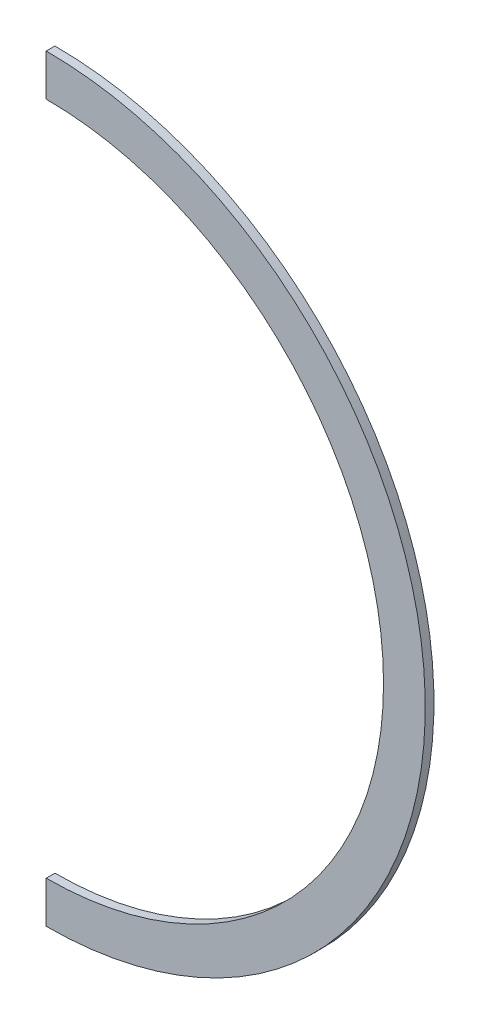
SolidWorks part; units mm, degrees
material "Balsa"
ref_plane "Front Plane" through (0, 0, 0) normal (0, 0, 1) x (1, 0, 0)
ref_plane "Top Plane" through (0, 0, 0) normal (0, 1, 0) x (1, 0, 0)
ref_plane "Right Plane" through (0, 0, 0) normal (1, 0, 0) x (0, 0, -1)
sketch "Sketch1" plane through (0, 0, 0) normal (0, 0, 1) x (1, 0, 0)
  line L0 (0, 32.094) -> (0, -346.2619) construction
  line L1 (0, 0) -> (0, 244.345) construction
  line L2 (0, 0) -> (0, 471.6969) construction
  line L3 (0, 0) -> (-283.5939, 0) construction
  line L4 (-127.2933, -32.5553) -> (-85.9841, -73.8644)
  line L5 (-85.9841, -73.8644) -> (-85.9841, -86.6438)
  line L6 (-85.9841, -73.8644) -> (-54.3993, -105.4493) construction
  arc A0 (-54.3993, -105.4493) -> (-127.2933, -32.5553) centre (0, 21.844) ccw
  arc A2 (-82.075, -89.6305) -> (-54.3993, -105.4493) centre (0, 21.844) ccw construction
  arc A3 (-127.2933, -32.5553) -> (-82.075, -89.6305) centre (0, 21.844) ccw construction
  arc A4 (-85.9841, -86.6438) -> (-54.3993, -105.4493) centre (0, 21.844) ccw
  spline S2 degree 3 poles (-1530.9406, -7642.7149) (259.0907, -1408.3953) (378.6573, 10.519) (49.9381, 150.9258) (45.7097, 152.4909) (37.1079, 155.2035) (32.7346, 156.3511) (27.1752, 157.5183) (26.0587, 157.7384) (23.8163, 158.1514) (22.6888, 158.3447) (19.306, 158.8811) (17.0511, 159.1813) (10.2867, 159.9126) (1.2693, 160.4377) (-7.745, 160.0789) (-14.5046, 159.4749) (-16.7575, 159.2176) (-20.1367, 158.7464) (-21.263, 158.5751) (-23.5156, 158.2037) (-24.6421, 158.0036) (-30.2426, 156.9366) (-34.6466, 155.8674) (-43.3063, 153.3113) (-47.562, 151.8242) (-55.9254, 148.4331) (-60.0331, 146.529) (-66.0807, 143.3516) (-68.0818, 142.2359) (-72.0044, 139.9197) (-73.9301, 138.7173) (-79.6017, 134.9792) (-86.884, 129.6473) (-93.6143, 123.6295) (-98.4521, 118.8554) (-100.0296, 117.2204) (-102.3424, 114.7015) (-103.1054, 113.8496) (-104.6077, 112.1297) (-105.3467, 111.2623) (-108.9818, 106.8875) (-111.6981, 103.2683) (-116.7574, 95.7975) (-119.1004, 91.9459) (-123.4121, 84.0098) (-125.3809, 79.9253) (-127.6006, 74.6695) (-128.0327, 73.61) (-128.8681, 71.4874) (-129.2719, 70.423) (-130.4422, 67.2205) (-131.1674, 65.0732) (-133.1812, 58.5951) (-135.4347, 49.861) (-136.834, 40.9354) (-137.5569, 34.168) (-137.7434, 31.9) (-137.9397, 28.4793) (-137.9911, 27.3374) (-138.0656, 25.0596) (-138.0887, 23.9223) (-138.135, 18.2442) (-137.9496, 13.7276) (-137.1441, 4.7454) (-136.5239, 0.2797) (-134.8456, -8.6005) (-133.7876, -13.015) (-131.2181, -21.791) (-129.7278, -26.0794) (-126.351, -34.4622) (-124.4643, -38.5569) (-120.2966, -46.5538) (-118.0156, -50.456) (-114.9122, -55.2108) (-114.2789, -56.1556) (-112.9868, -58.0327) (-112.3272, -58.9661) (-110.315, -61.7398) (-108.9333, -63.5482) (-104.6702, -68.8537) (-98.6716, -75.6089) (-92.0553, -81.7381) (-86.8592, -86.0978) (-85.0881, -87.5114) (-82.3719, -89.5716) (-81.4566, -90.2482) (-79.6058, -91.5811) (-78.6696, -92.238) (312.7351, -359.6403) (1980.7618, 1435.5712) (5240.7041, 5800.1077) knots -2.409432 -2.409432 -2.409432 -2.409432 0.03125 0.03125 0.0625 0.0625 0.09375 0.09375 0.101563 0.101563 0.109375 0.109375 0.125 0.125 0.15625 0.1875 0.1875 0.203125 0.203125 0.210937 0.210937 0.21875 0.21875 0.25 0.25 0.28125 0.28125 0.3125 0.3125 0.328125 0.328125 0.34375 0.34375 0.375 0.40625 0.40625 0.421875 0.421875 0.429687 0.429687 0.4375 0.4375 0.46875 0.46875 0.5 0.5 0.53125 0.53125 0.539062 0.539062 0.546875 0.546875 0.5625 0.5625 0.59375 0.625 0.625 0.640625 0.640625 0.648437 0.648437 0.65625 0.65625 0.6875 0.6875 0.71875 0.71875 0.75 0.75 0.78125 0.78125 0.8125 0.8125 0.84375 0.84375 0.851562 0.851562 0.859375 0.859375 0.875 0.875 0.90625 0.9375 0.9375 0.953125 0.953125 0.960937 0.960937 0.96875 0.96875 4.2021 4.2021 4.2021 4.2021 only from (66.3397, 143.1887) to (-66.0465, -100.0388)
  spline S3 degree 3 poles (66.3397, 143.1887) (62.3323, 145.3909) (58.2494, 147.3758) (49.9381, 150.9258) (45.7097, 152.4909) (37.1079, 155.2035) (32.7346, 156.3511) (27.1752, 157.5183) (26.0587, 157.7384) (23.8163, 158.1514) (22.6888, 158.3447) (19.306, 158.8811) (17.0511, 159.1813) (10.2867, 159.9126) (1.2693, 160.4377) (-7.745, 160.0789) (-14.5046, 159.4749) (-16.7575, 159.2176) (-20.1367, 158.7464) (-21.263, 158.5751) (-23.5156, 158.2037) (-24.6421, 158.0036) (-30.2426, 156.9366) (-34.6466, 155.8674) (-43.3063, 153.3113) (-47.562, 151.8242) (-55.9254, 148.4331) (-60.0331, 146.529) (-66.0807, 143.3516) (-68.0818, 142.2359) (-72.0044, 139.9197) (-73.9301, 138.7173) (-79.6017, 134.9792) (-86.884, 129.6473) (-93.6143, 123.6295) (-98.4521, 118.8554) (-100.0296, 117.2204) (-102.3424, 114.7015) (-103.1054, 113.8496) (-104.6077, 112.1297) (-105.3467, 111.2623) (-108.9818, 106.8875) (-111.6981, 103.2683) (-116.7574, 95.7975) (-119.1004, 91.9459) (-123.4121, 84.0098) (-125.3809, 79.9253) (-127.6006, 74.6695) (-128.0327, 73.61) (-128.8681, 71.4874) (-129.2719, 70.423) (-130.4422, 67.2205) (-131.1674, 65.0732) (-133.1812, 58.5951) (-135.4347, 49.861) (-136.834, 40.9354) (-137.5569, 34.168) (-137.7434, 31.9) (-137.9397, 28.4793) (-137.9911, 27.3374) (-138.0656, 25.0596) (-138.0887, 23.9223) (-138.135, 18.2442) (-137.9496, 13.7276) (-137.1441, 4.7454) (-136.5239, 0.2797) (-134.8456, -8.6005) (-133.7876, -13.015) (-131.2181, -21.791) (-129.7278, -26.0794) (-127.6847, -31.1513) (-127.3213, -32.0275) (-126.9491, -32.8995) knots 0 0 0 0 0.03125 0.03125 0.0625 0.0625 0.09375 0.09375 0.101563 0.101563 0.109375 0.109375 0.125 0.125 0.15625 0.1875 0.1875 0.203125 0.203125 0.210937 0.210937 0.21875 0.21875 0.25 0.25 0.28125 0.28125 0.3125 0.3125 0.328125 0.328125 0.34375 0.34375 0.375 0.40625 0.40625 0.421875 0.421875 0.429687 0.429687 0.4375 0.4375 0.46875 0.46875 0.5 0.5 0.53125 0.53125 0.539062 0.539062 0.546875 0.546875 0.5625 0.5625 0.59375 0.625 0.625 0.640625 0.640625 0.648437 0.648437 0.65625 0.65625 0.6875 0.6875 0.71875 0.71875 0.75 0.75 0.78125 0.78125 0.787815 0.787815 0.787815 0.787815 construction
  point P2 (0, 160.2226)
  point P3 (0, -116.9127)
  point P23 (-85.9841, -73.8644)
  dimension "D1" = 277.1353
  dimension "D2" = 276.86
  dimension "D3" = 21.844
  dimension "D5" = 45
  dimension "D6" = 113.03
  dimension "D4" = 58.42
  dimension "D7" = 45
extrude "Boss-Extrude1" add sketch "Sketch1" along normal mid plane 3.175
sketch "Sketch2" plane through (0, 0, 1.5875) normal (0, 0, 1) x (1, 0, 0)
  line L4 (-114.3729, -23.9231) -> (-70.7441, -67.5518)
  line L5 (-70.7441, -67.5518) -> (-70.7441, -79.0076)
  line L6 (-114.3729, -23.9231) -> (-70.7441, -67.5518)
  line L7 (-70.7441, -67.5518) -> (-70.7441, -79.0076)
  arc A2 (-70.7441, -79.0076) -> (-114.3729, -23.9231) centre (0, 21.844) ccw
  arc A3 (-70.7441, -79.0076) -> (-114.3729, -23.9231) centre (0, 21.844) ccw
  dimension "D1" = 15.24
extrude "Cut-Extrude1" cut sketch "Sketch2" against normal up to surface (3.175 mm away) up to face at (-27.5361, -9.1994, -1.5875)
fillet "Fillet1" radius 8.89 6 edges at (-127.2933, -32.5553, 0) (-114.3729, -23.9231, 0) (-85.9841, -73.8644, 0) (-85.9841, -86.6438, 0) (-70.7441, -67.5518, 0) (-70.7441, -79.0076, 0)
sketch "Sketch3" plane through (0, 0, 1.5875) normal (0, 0, 1) x (1, 0, 0)
  line L0 (-0.0002, 49.9919) -> (-0.0176, 733.2) construction
  line L1 (-0.0002, 49.9919) -> (-0.0176, 733.2) construction
  line L2 (-136.2041, -28.3557) -> (-0.0002, 49.9919) construction
  line L3 (136.2076, -28.3488) -> (-0.0002, 49.9919) construction
  line L4 (-136.2041, -28.3557) -> (-0.0002, 49.9919) construction
  line L5 (136.2076, -28.3488) -> (-0.0002, 49.9919) construction
  line L6 (-1.6539, 152.6441) -> (-1.654, 160.2641)
  line L7 (1.6481, 152.6442) -> (1.648, 160.2642)
  line L8 (-1.6539, 152.6441) -> (1.6481, 152.6442)
  line L9 (119.8485, -45.962) -> (106.7537, -38.3747)
  line L10 (121.4435, -43.2066) -> (108.3479, -35.6188)
  line L11 (-126.0584, -33.7901) -> (-88.588, -71.2606)
  line L12 (-85.9841, -77.5468) -> (-85.9841, -82.2574)
  line L13 (-126.0584, -33.7901) -> (-88.588, -71.2606) construction
  line L14 (-85.9841, -77.5468) -> (-85.9841, -82.2574) construction
  line L18 (121.4435, -43.2066) -> (108.3479, -35.6188)
  line L30 (-123.167, -47.8929) -> (-104.8722, -37.2914)
  line L35 (119.8485, -45.962) -> (106.7537, -38.3747)
  line L47 (108.5244, -35.721) -> (120.1169, -46.1175) construction
  line L48 (114.3206, -40.9193) -> (126.5619, -48.0121) construction
  line L49 (113.8577, -42.5592) -> (122.0137, -47.2849)
  line L50 (115.5132, -39.7021) -> (123.6691, -44.4278)
  line L51 (113.8577, -42.5592) -> (115.5132, -39.7021)
  line L52 (122.0137, -47.2849) -> (123.6691, -44.4278)
  line L58 (-124.7703, -45.1423) -> (-106.4681, -34.5364)
  line L59 (-124.7703, -45.1423) -> (-123.167, -47.8929)
  line L71 (-124.7703, -45.1423) -> (-123.167, -47.8929) construction
  line L72 (-124.7703, -45.1423) -> (-106.4681, -34.5364) construction
  line L73 (-123.167, -47.8929) -> (-104.8722, -37.2914) construction
  line L74 (-123.167, -47.8929) -> (-107.9499, -35.3951) construction
  line L75 (-115.5584, -41.644) -> (-110.9064, -38.9482) construction
  line L76 (-119.3826, -41.9518) -> (-112.6266, -38.0369)
  line L77 (-117.727, -44.8088) -> (-110.971, -40.8938)
  line L78 (-119.3826, -41.9518) -> (-117.727, -44.8088)
  line L79 (-112.6266, -38.0369) -> (-110.971, -40.8938)
  arc A0 (-54.3993, -105.4493) -> (-127.2933, -32.5553) centre (0, 21.844) ccw construction
  arc A2 (-1.654, 160.2641) -> (-130.2816, -24.9489) centre (0, 21.844) ccw construction
  arc A3 (-130.2816, -24.9489) -> (-127.2933, -32.5553) centre (0, 21.844) ccw construction
  arc A4 (-1.654, 160.2641) -> (-130.2816, -24.9489) centre (0, 21.844) ccw construction
  arc A5 (-130.2816, -24.9489) -> (-127.9919, -30.8906) centre (0, 21.844) ccw construction
  arc A6 (-82.3849, -89.4016) -> (-127.9919, -30.8906) centre (0, 21.844) ccw
  arc A7 (-127.9919, -30.8906) -> (-126.0584, -33.7901) centre (-119.7722, -27.504) ccw
  arc A8 (-85.9841, -77.5468) -> (-88.588, -71.2606) centre (-94.8741, -77.5468) ccw
  arc A9 (-85.9841, -82.2574) -> (-82.3849, -89.4016) centre (-77.0941, -82.2574) ccw
  arc A11 (-127.9919, -30.8906) -> (-126.0584, -33.7901) centre (-119.7722, -27.504) ccw construction
  arc A12 (-85.9841, -77.5468) -> (-88.588, -71.2606) centre (-94.8741, -77.5468) ccw construction
  arc A13 (-85.9841, -82.2574) -> (-82.3849, -89.4016) centre (-77.0941, -82.2574) ccw construction
  arc A14 (130.2841, -24.9419) -> (1.648, 160.2642) centre (0, 21.844) ccw construction
  arc A15 (1.648, 160.2642) -> (-1.654, 160.2641) centre (0, 21.844) ccw
  arc A16 (130.2841, -24.9419) -> (1.648, 160.2642) centre (0, 21.844) ccw construction
  arc A17 (1.648, 160.2642) -> (-1.654, 160.2641) centre (0, 21.844) ccw
  spline S0 degree 3 poles (106.7537, -38.3747) (107.2851, -37.456) (107.8165, -36.5374) (108.3479, -35.6188) knots 0 0 0 0 1 1 1 1 weights 1 1 1 1
  spline S1 degree 3 poles (119.8485, -45.962) (120.3802, -45.0435) (120.9118, -44.1251) (121.4435, -43.2066) knots 0 0 0 0 1 1 1 1 weights 1 1 1 1
  spline S2 degree 3 poles (-885.9096, -1769.7959) (-211.5315, -623.0099) (457.4335, 532.6653) (1115.294, 1687.3986) knots -628.025755 -628.025755 -628.025755 -628.025755 629.32196 629.32196 629.32196 629.32196 weights 1.00213 0.999289 0.99929 1.002132 only from (119.8485, -45.962) to (121.4435, -43.2066)
  spline S3 degree 3 poles (-1102.963, 1696.4301) (-441.8978, 540.8873) (227.2768, -614.259) (901.012, -1762.8827) knots -628.210575 -628.210575 -628.210575 -628.210575 629.142222 629.142222 629.142222 629.142222 weights 1.001328 0.999558 0.999557 1.001327 only from (-106.4681, -34.5364) to (-104.8722, -37.2914)
  spline S4 degree 3 poles (-106.4681, -34.5364) (-105.9361, -35.4547) (-105.4042, -36.373) (-104.8722, -37.2914) knots 0 0 0 0 1 1 1 1 weights 1 1 1 1 construction
  spline S6 degree 3 poles (-898.3985, -1763.0369) (-224.3104, -615.0446) (444.2624, 540.7506) (1102.1878, 1695.4772) knots -627.922228 -627.922228 -627.922228 -627.922228 629.425892 629.425892 629.425892 629.425892 weights 1.001921 0.999359 0.99936 1.001924 only from (106.7537, -38.3747) to (108.3479, -35.6188)
  point P49 (-116.0256, -43.8229)
  point P50 (120.451, -46.3794)
  arc M19 (-82.3849, -89.4016) -> (-127.9919, -30.8906) centre (0, 21.844) ccw
  line M21 (-126.0584, -33.7901) -> (-88.588, -71.2606)
  dimension "D1" = 3.302
  dimension "D2" = 7.62
  dimension "D4" = 3.302
  dimension "D5" = 7.62
  dimension "D6" = 3.302
  dimension "D7" = 5.842
  dimension "D3" = 0
extrude "Cut-Extrude2" [suppressed] cut sketch "Sketch3" against normal through all contours L79 L76 L77 M21 | L6 L8 L7 M19 | L51 L49 L50 M19
sketch "Sketch4" plane through (0, 0, 0) normal (1, 0, 0) x (0, 0, -1)
  line L1 (-96.2805, 232.7957) -> (122.2438, 232.7957)
  line L2 (-96.2805, 232.7957) -> (-96.2805, -207.8589)
  line L3 (-96.2805, -207.8589) -> (122.2438, -207.8589)
  line L4 (122.2438, 232.7957) -> (122.2438, -207.8589)
extrude "Cut-Extrude3" cut sketch "Sketch4" against normal through all
equation "\"a\"= 0.06"
equation "\"slotwidth\"=0.13"
equation "\"slotheight\"=0.3"
